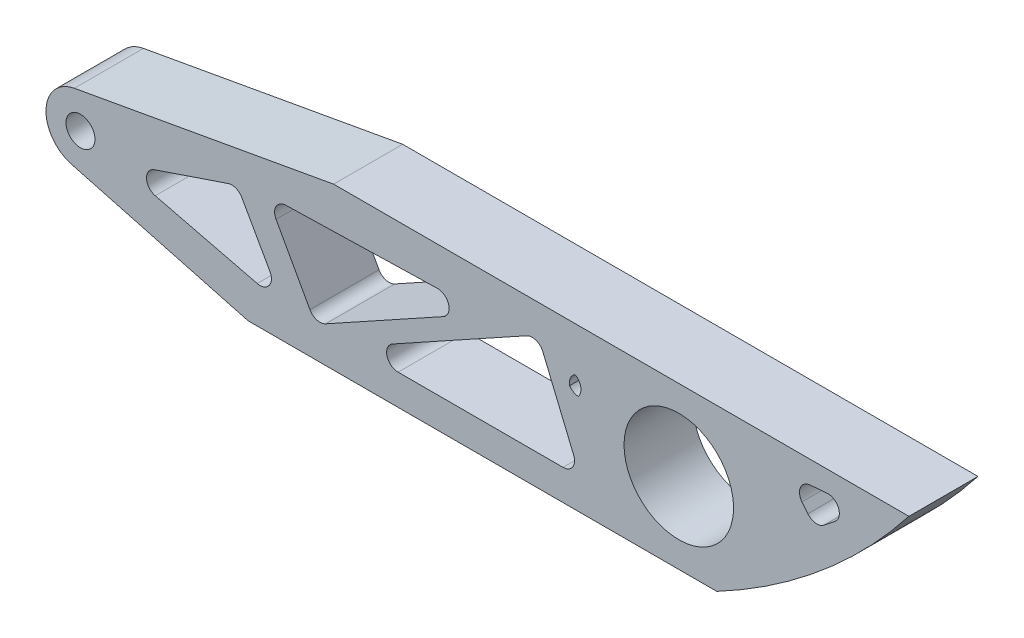
SolidWorks part; units mm, degrees
ref_plane "Front Plane" through (0, 0, 0) normal (0, 0, 1) x (1, 0, 0)
ref_plane "Top Plane" through (0, 0, 0) normal (0, 1, 0) x (1, 0, 0)
ref_plane "Right Plane" through (0, 0, 0) normal (1, 0, 0) x (0, 0, -1)
sketch "Sketch1" plane through (0, 0, 0) normal (0, 0, 1) x (1, 0, 0)
  line L1 (120.65, 22.225) -> (-120.65, 22.225)
  line L2 (120.65, 22.225) -> (120.65, -22.225)
  line L3 (120.65, -22.225) -> (-120.65, -22.225)
  line L4 (-120.65, 22.225) -> (-120.65, -22.225)
  line L5 (120.65, 22.225) -> (-120.65, -22.225) construction
  line L6 (120.65, -22.225) -> (-120.65, 22.225) construction
  point P0 (0, 0)
  dimension "D1" = 241.3
  dimension "D2" = 44.45
extrude "Boss-Extrude1" add sketch "Sketch1" along normal blind 19.06
sketch "Sketch3" plane through (0, 0, 19.06) normal (0, 0, 1) x (1, 0, 0)
  line L0 (0, 0) -> (-120.65, 0) construction
  line L1 (-120.65, 22.225) -> (-120.65, -22.225) construction
  circle A0 centre (-107.95, 0) radius 4
  dimension "D2" = 8
  dimension "D1" = 12.7
extrude "Cut-Extrude1" cut sketch "Sketch3" against normal through all
sketch "Sketch5" plane through (0, 0, 19.06) normal (0, 0, 1) x (1, 0, 0)
  line L0 (-120.65, -22.225) -> (120.65, -22.225) construction
  line L1 (-110.4107, -9.2017) -> (-61.7102, -22.225)
  line L2 (-109.6341, 9.3749) -> (-38.1, 22.225)
  line L3 (120.65, 22.225) -> (-120.65, 22.225) construction
  line L4 (-38.1, 22.225) -> (-120.65, 22.225)
  line L5 (-120.65, 22.225) -> (-120.65, -22.225)
  line L6 (-120.65, -22.225) -> (-61.7102, -22.225)
  line L7 (120.65, 22.225) -> (120.65, -22.225)
  line L8 (120.65, -22.225) -> (67.6371, -22.225)
  arc A0 (67.6371, -22.225) -> (120.65, 22.225) centre (-9.5799, 123.7049) ccw
  arc A2 (-109.6341, 9.3749) -> (-110.4107, -9.2017) centre (-107.95, 0) ccw
  line M3 (-120.65, 22.225) -> (-120.65, -22.225)
  line M4 (-120.65, -22.225) -> (120.65, -22.225)
  line M5 (120.65, -22.225) -> (120.65, 22.225)
  line M6 (120.65, 22.225) -> (-120.65, 22.225)
  dimension "D1" = 165.1
  dimension "D2" = 19.05
  dimension "D3" = 82.55
extrude "Cut-Extrude2" cut sketch "Sketch5" against normal through all contours A0 L8 M5 | A2 L2 L1 M6 M3 M4 region at (-86.3027, -16.6191, 19.06) region at (104.3043, -8.4634, 19.06)
sketch "Sketch6" plane through (0, 0, 19.06) normal (0, 0, 1) x (1, 0, 0)
  line L0 (-107.95, 0) -> (99.7595, 0) construction
  arc A0 (67.6371, -22.225) -> (120.65, 22.225) centre (-9.5799, 123.7049) ccw construction
sketch "Sketch11" plane through (0, 0, 0) normal (0, 0, -1) x (-1, 0, 0)
  line L1 (107.95, 0) -> (-99.7595, 0) construction
  circle A1 centre (-57.15, 0) radius 15.113
  circle A2 centre (107.95, 0) radius 4 construction
  dimension "D1" = 30.226
  dimension "D2" = 165.1
extrude "Cut-Extrude3" cut sketch "Sketch11" against normal through all
sketch "Sketch12" plane through (0, 0, 0) normal (0, 0, -1) x (-1, 0, 0)
  line L3 (62.1778, -29.4105) -> (46.0432, -22.2176)
  line L5 (46.0432, -22.2176) -> (70.9328, -9.772)
  line L6 (70.9328, -9.772) -> (62.1778, -29.4105)
  dimension "D1" = 90
extrude "Boss-Extrude2" [suppressed] add sketch "Sketch12" against normal up to surface (19.06 mm away) up to face at (42.037, 0, 19.06)
sketch "Sketch14" plane through (0, 0, 19.06) normal (0, 0, 1) x (1, 0, 0)
  line L0 (87.4273, 15.5587) -> (94.742, 6.4153)
  line L1 (94.742, 6.4153) -> (108.4371, 17.3503)
  line L2 (108.4371, 17.3503) -> (87.4273, 15.5587)
  line L3 (18.2585, 14.338) -> (29.9735, -13.8007)
  line L5 (29.9735, -13.8007) -> (-32.6065, -13.8007)
  line L6 (-32.6065, -13.8007) -> (18.2585, 14.338)
  line L9 (-43.1009, -13.8007) -> (3.4683, 11.9615)
  line L10 (-64.7308, 8.6621) -> (-52.0681, -13.8007)
  line L11 (-52.0681, -13.8007) -> (-97.91, -2.5585)
  line L12 (-97.91, -2.5585) -> (-64.7308, 8.6621)
  line L14 (25.3772, 10.4563) -> (27.9586, 4.2561)
  line L15 (27.9586, 4.2561) -> (42.8511, 10.4563)
  line L16 (42.8511, 10.4563) -> (25.3772, 10.4563)
  line L17 (47.7718, 17.2115) -> (29.7305, 0) construction
  line L18 (-107.95, 0) -> (99.7595, 0) construction
  line L19 (29.7305, 0) -> (35.4762, -13.8007) construction
  line L23 (-43.1009, -13.8007) -> (-56.52, 10.4563)
  line L24 (-56.52, 10.4563) -> (3.4683, 11.9615)
  dimension "D1" = 8.9672
  dimension "D3" = 5.08
  dimension "D5" = 30.48
  dimension "D6" = 5.08
  dimension "D7" = 68.952
extrude "Cut-Extrude5" cut sketch "Sketch14" against normal through all
fillet "Fillet1" radius 3.175 15 edges at (-64.7308, 8.6621, 9.53) (-52.0681, -13.8007, 9.53) (-97.91, -2.5585, 9.53) (-56.52, 10.4563, 9.53) (3.4683, 11.9615, 9.53) (-43.1009, -13.8007, 9.53) (-32.6065, -13.8007, 9.53) (18.2585, 14.338, 9.53) (29.9735, -13.8007, 9.53) (87.4273, 15.5587, 9.53) (108.4371, 17.3503, 9.53) (94.742, 6.4153, 9.53) (27.9586, 4.2561, 9.53) (42.8511, 10.4563, 9.53) (25.3772, 10.4563, 9.53)
sketch "Sketch15" plane through (0, 0, 0) normal (0, 0, -1) x (-1, 0, 0)
  line L0 (61.7102, -22.225) -> (117.4667, -22.225) construction
  line L1 (117.4667, -22.225) -> (117.4667, 0.3979) construction
  arc A0 (110.4107, -9.2017) -> (109.6341, 9.3749) centre (107.95, 0) ccw construction
